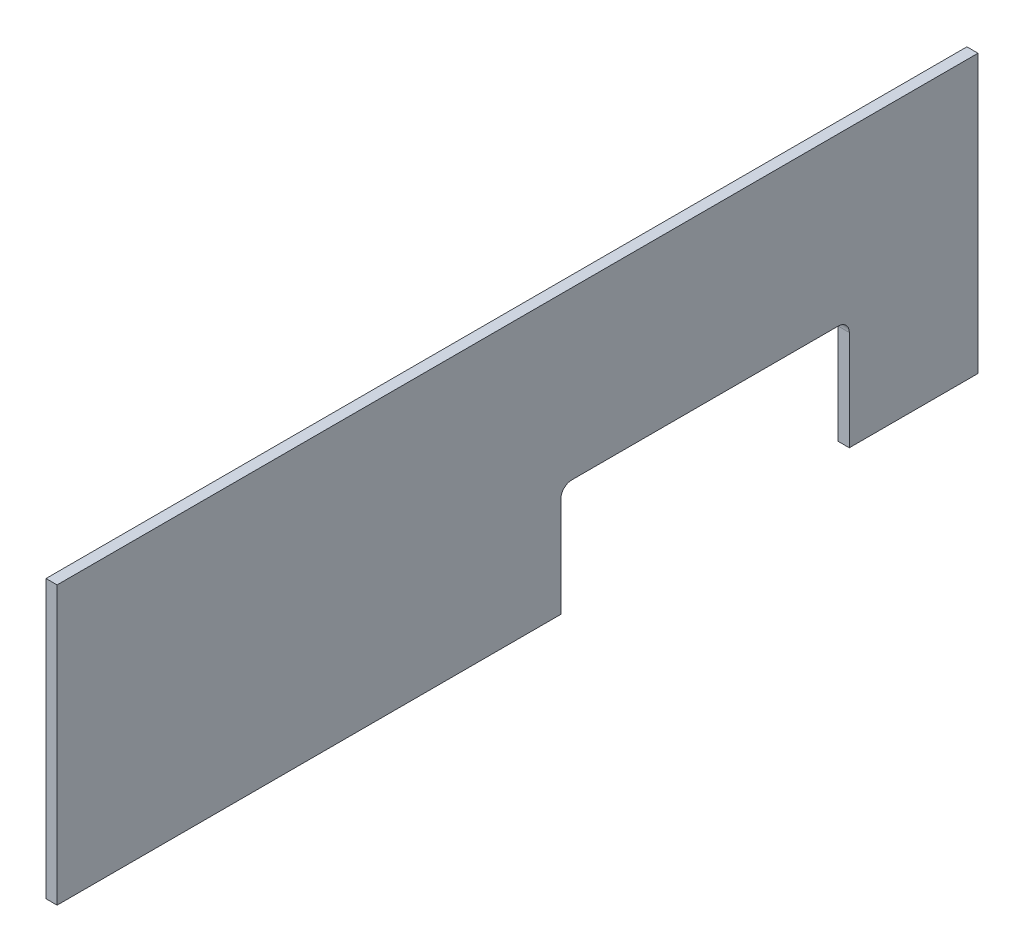
SolidWorks part; units mm, degrees
ref_plane "Front Plane" through (0, 0, 0) normal (0, 0, 1) x (1, 0, 0)
ref_plane "Top Plane" through (0, 0, 0) normal (0, 1, 0) x (1, 0, 0)
ref_plane "Right Plane" through (0, 0, 0) normal (1, 0, 0) x (0, 0, -1)
sketch "Sketch1" plane through (0, 0, 0) normal (1, 0, 0) x (0, 0, -1)
  line L1 (-41.5, -12.5) -> (41.5, -12.5)
  line L2 (-41.5, -12.5) -> (-41.5, 12.5)
  line L3 (-41.5, 12.5) -> (41.5, 12.5)
  line L4 (41.5, -12.5) -> (41.5, 12.5)
  line L5 (-41.5, -12.5) -> (41.5, 12.5) construction
  line L6 (-41.5, 12.5) -> (41.5, -12.5) construction
  line L7 (3.9, -12.5) -> (29.9, -12.5)
  line L8 (3.9, -12.5) -> (3.9, -2.5)
  line L9 (3.9, -2.5) -> (29.9, -2.5)
  line L10 (29.9, -12.5) -> (29.9, -2.5)
  point P0 (0, 0)
  dimension "D1" = 25
  dimension "D2" = 83
  dimension "D3" = 26
  dimension "D4" = 10
  dimension "D5" = 11.6
extrude "Boss-Extrude1" add sketch "Sketch1" along normal blind 1 contours L10 L1 L4 L3 L2 L8 L9 region at (0, 1.0744, 2.4209)
fillet "Fillet1" radius 1 2 edges at (0.5, -2.5, -29.9) (0.5, -2.5, -3.9)
